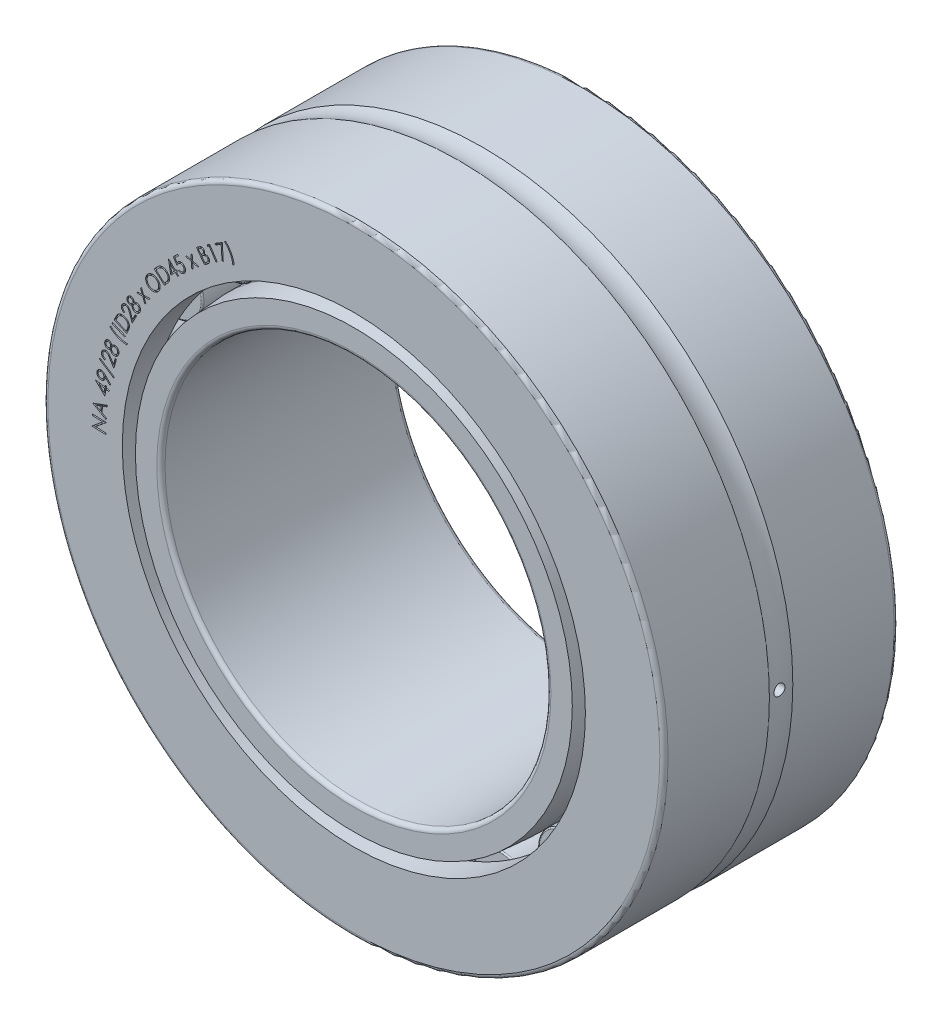
SolidWorks part; units mm, degrees
material "SPRING STEEL ASTM A 229"
ref_plane "Front Plane" through (0, 0, 0) normal (0, 0, 1) x (1, 0, 0)
ref_plane "Top Plane" through (0, 0, 0) normal (0, 1, 0) x (1, 0, 0)
ref_plane "Right Plane" through (0, 0, 0) normal (1, 0, 0) x (0, 0, -1)
sketch "Sketch2" plane through (0, 0, 0) normal (1, 0, 0) x (0, 0, -1)
  line L0 (0, 0) -> (14.7851, 0) construction
  line L1 (0, 0) -> (0, 28) construction
  line L2 (-8.2, 22.5) -> (-0.85, 22.5)
  line L3 (8.5, 22.2) -> (8.5, 16.8)
  line L4 (8.5, 16.8) -> (6.4, 16.8)
  line L5 (-6.4, 20) -> (-6.4, 16.8)
  line L6 (6.4, 20) -> (6.4, 16.8)
  line L7 (8.5, 15.85) -> (8.5, 14)
  line L8 (8.5, 14) -> (-8.5, 14)
  line L9 (-8.5, 15.85) -> (-8.5, 14)
  line L12 (-8.5, 16.8) -> (-6.4, 16.8)
  line L13 (-8.5, 22.2) -> (-8.5, 16.8)
  line L15 (0.85, 22.5) -> (8.2, 22.5)
  line L16 (-6.4, 20) -> (6.4, 20)
  line L18 (-6.4, 16) -> (6.4, 16)
  line L28 (-8.5, 15.85) -> (-6.4, 16)
  line L29 (8.5, 15.85) -> (6.4, 16)
  arc A0 (-0.85, 22.5) -> (0.85, 22.5) centre (0, 24.8511) ccw
  arc A1 (-8.5, 22.2) -> (-8.2, 22.5) centre (-8.2, 22.2) cw
  arc A2 (8.2, 22.5) -> (8.5, 22.2) centre (8.2, 22.2) cw
  point P10 (-8.5, 22.5)
  point P13 (0, 14)
  point P18 (0, 27.5)
  point P23 (8.5, 22.5)
  dimension "D1" = 5
  dimension "D8" = 40
  dimension "D12" = 0.3
  dimension "D2" = 17
  dimension "D3" = 28
  dimension "D4" = 2.1
  dimension "D5" = 45
  dimension "D6" = 32
  dimension "D7" = 12.8
  dimension "D9" = 33.6
  dimension "D10" = 1.7
  dimension "D11" = 31.7
revolve "Revolve1" add sketch "Sketch2" angle 360 about L0
fillet "Fillet1" radius 0.3 2 edges at (14, 0, 8.5) (14, 0, -8.5)
sketch "Sketch3" plane through (0, 0, 0) normal (1, 0, 0) x (0, 0, -1)
  circle A0 centre (0, 0) radius 0.4
  dimension "D1" = 0.8
extrude "Extrude3" cut sketch "Sketch3" along normal up to next from offset 19
sketch "Sketch4" plane through (0, 0, 8.5) normal (0, 0, -1) x (-1, 0, 0)
  circle A0 centre (0, 0) radius 18 construction
  text T0 "NA 49/28 (ID28 x OD45 x B17)" font "Century Gothic" height 1
  dimension "D1" = 36
extrude "Extrude4" cut sketch "Sketch4" along normal blind 0.1
sketch "Sketch5" plane through (0, 0, 0) normal (1, 0, 0) x (0, 0, -1)
  line L0 (6.4, 20) -> (6.4, -20) construction
  line L1 (-6.3, 20.01) -> (6.3, 20.01)
  line L2 (-6.4, 19.91) -> (-6.4, 18.01)
  line L3 (-6.4, 18.01) -> (6.4, 18.01) construction
  line L4 (6.4, 19.91) -> (6.4, 18.01)
  line L5 (6.4, 18.01) -> (-6.4, 18.01)
  arc A0 (6.3, 20.01) -> (6.4, 19.91) centre (6.3, 19.91) cw
  arc A1 (-6.3, 20.01) -> (-6.4, 19.91) centre (-6.3, 19.91) ccw
  dimension "D3" = 0.1
  dimension "D1" = 4
  dimension "D2" = 12.8
  dimension "D4" = 18.01
revolve "Revolve3" add sketch "Sketch5" angle 360 about L3
pattern_circular "CirPattern1" count 19 over 360 about axis through (0, 0, 0) along (0, 0, 1) of "Revolve3"
